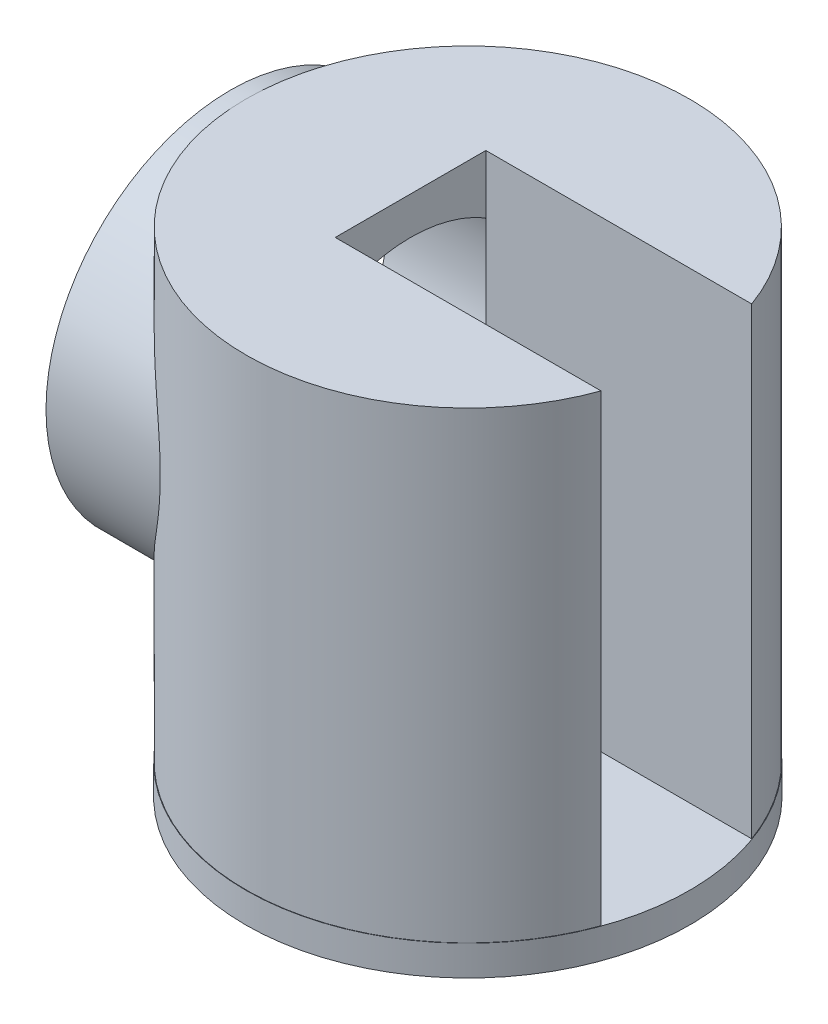
SolidWorks part; units mm, degrees
ref_plane "Спереди" through (0, 0, 0) normal (0, 0, 1) x (1, 0, 0)
ref_plane "Сверху" through (0, 0, 0) normal (0, 1, 0) x (1, 0, 0)
ref_plane "Справа" through (0, 0, 0) normal (1, 0, 0) x (0, 0, -1)
sketch "Эскиз1" plane through (0, 0, 0) normal (0, 1, 0) x (1, 0, 0)
  circle A0 centre (0, 0) radius 29.5
  dimension "D1" = 59
extrude "Бобышка-Вытянуть1" add sketch "Эскиз1" along normal blind 4
sketch "Эскиз2" plane through (0, 4, 0) normal (0, 1, 0) x (1, 0, 0)
  circle A0 centre (7, 0) radius 1.5
  dimension "D2" = 3
  dimension "D1" = 7
extrude "Вырез-Вытянуть1" cut sketch "Эскиз2" against normal through all
pattern_circular "Круговой массив1" count 4 over 360 about axis through (0, 4, 0) along (0, 1, 0) of "Вырез-Вытянуть1"
sketch "Эскиз3" plane through (0, 4, 0) normal (0, 1, 0) x (1, 0, 0)
  circle A0 centre (0, 0) radius 29.4449
extrude "Бобышка-Вытянуть2" add sketch "Эскиз3" along normal blind 61.5
sketch "Эскиз4" plane through (0, 65.5, 0) normal (0, 1, 0) x (1, 0, 0)
  line L0 (0, 0) -> (41.3001, 0) construction
  line L2 (-7.6, 10) -> (31.9, 10)
  line L3 (-7.6, 10) -> (-7.6, -10)
  line L4 (-7.6, -10) -> (31.9, -10)
  line L5 (31.9, 10) -> (31.9, -10)
  dimension "D1" = 7.6
  dimension "D2" = 39.5
  dimension "D3" = 20
  dimension "D4" = 10
extrude "Вырез-Вытянуть2" cut sketch "Эскиз4" against normal blind 61.5
sketch "Эскиз7" plane through (0, 0, 0) normal (1, 0, 0) x (0, 0, -1)
  circle A0 centre (0, 41) radius 21
  circle A1 centre (0, 41) radius 24.5
  dimension "D2" = 42
  dimension "D3" = 49
  dimension "D1" = 41
extrude "Бобышка-Вытянуть3" add sketch "Эскиз7" against normal blind 21.5 from offset 10 offset against normal yes
sketch "Эскиз11" plane through (-31.5, 0, 0) normal (-1, 0, 0) x (0, 0, 1)
  circle A0 centre (0, 41) radius 21
  dimension "D2" = 42
  dimension "D1" = 41
extrude "Вырез-Вытянуть7" cut sketch "Эскиз11" against normal blind 17
sketch "Эскиз12" plane through (-31.5, 0, 0) normal (-1, 0, 0) x (0, 0, 1)
  circle A0 centre (0, 41) radius 19.5
  dimension "D2" = 39
  dimension "D1" = 41
extrude "Вырез-Вытянуть10" cut sketch "Эскиз12" against normal up to surface (23.9 mm away) up to face at (-7.6, 24.5, 0)
